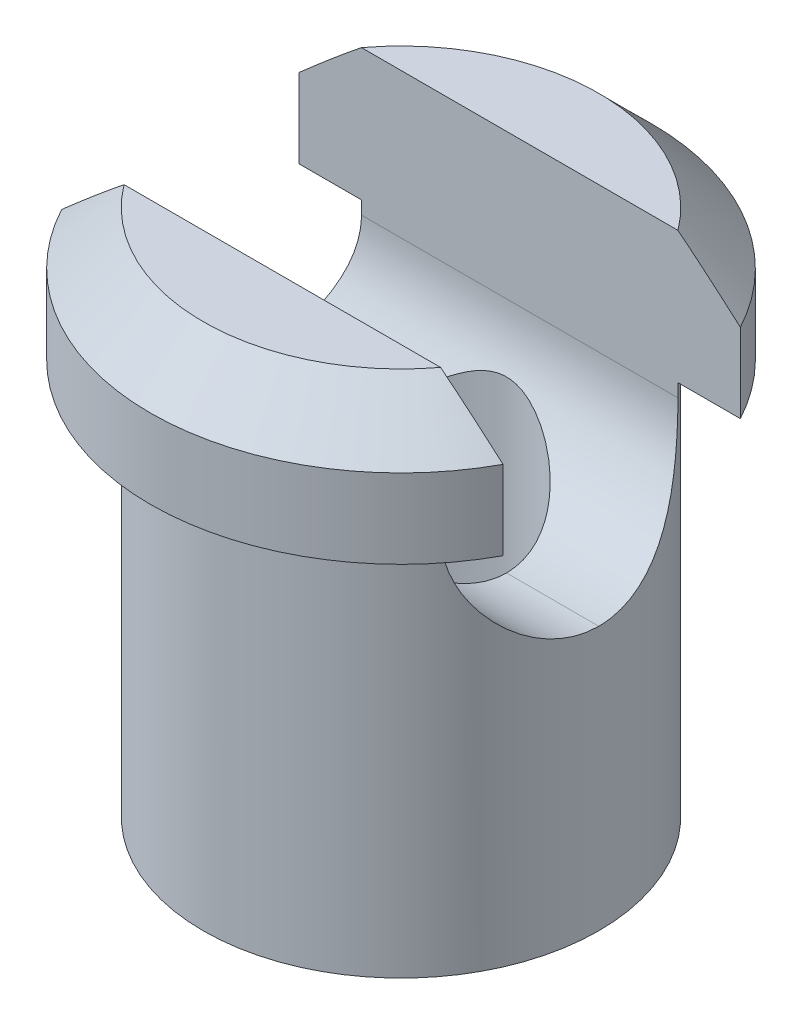
SolidWorks part; units mm, degrees
ref_plane "Front Plane" through (0, 0, 0) normal (0, 0, 1) x (1, 0, 0)
ref_plane "Top Plane" through (0, 0, 0) normal (0, 1, 0) x (1, 0, 0)
ref_plane "Right Plane" through (0, 0, 0) normal (1, 0, 0) x (0, 0, -1)
sketch "Sketch1" plane through (0, 0, 0) normal (0, 0, 1) x (1, 0, 0)
  line L0 (0, 0) -> (7.5, 0)
  line L1 (7.5, 0) -> (7.5, 15)
  line L2 (7.5, 15) -> (9.5, 15)
  line L3 (9.5, 15) -> (9.5, 18)
  line L4 (9.5, 18) -> (7.5, 20)
  line L5 (7.5, 20) -> (0, 20)
  line L6 (0, 20) -> (0, 0)
  dimension "D1" = 7.5
  dimension "D2" = 15
  dimension "D3" = 3
  dimension "D4" = 5
  dimension "D5" = 2
  dimension "D6" = 135
revolve "Revolve1" add sketch "Sketch1" angle 360 about L6
sketch "Sketch2" plane through (0, 0, 0) normal (0, -1, 0) x (1, 0, 0)
  circle A0 centre (0, 0) radius 4
  dimension "D1" = 8
extrude "Cut-Extrude1" cut sketch "Sketch2" against normal through all
sketch "Sketch3" plane through (0, 0, 0) normal (1, 0, 0) x (0, 0, -1)
  line L0 (7.5, 20) -> (-7.5, 20) construction
  line L1 (-4.5, 20) -> (4.5, 20)
  line L2 (-4.5, 20) -> (-4.5, 10)
  line L3 (-4.5, 10) -> (4.5, 10)
  line L4 (4.5, 20) -> (4.5, 10)
  point P6 (4.8238, 7.1007)
  point P7 (0, 10)
  dimension "D1" = 10
  dimension "D2" = 9
extrude "Cut-Extrude2" cut sketch "Sketch3" against normal through all both and the other way through all
fillet "Fillet1" radius 4.5 2 edges at (0, 10, 4.5) (0, 10, -4.5)
